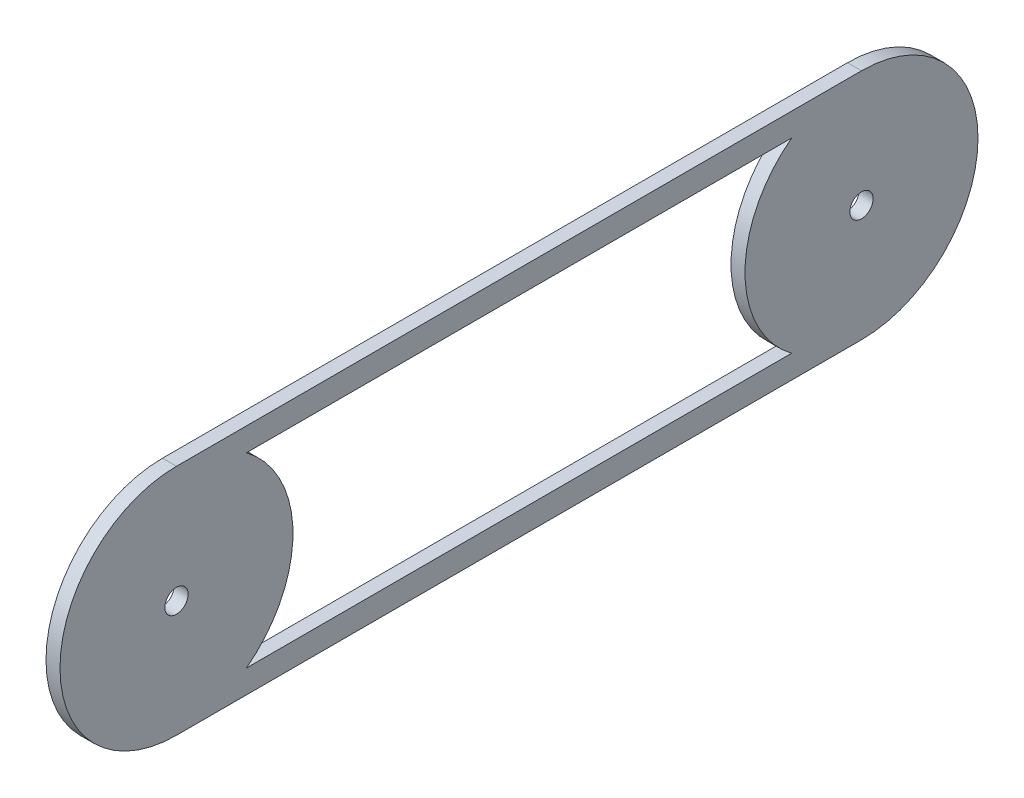
SolidWorks part; units mm, degrees
ref_plane "Front Plane" through (0, 0, 0) normal (0, 0, 1) x (1, 0, 0)
ref_plane "Top Plane" through (0, 0, 0) normal (0, 1, 0) x (1, 0, 0)
ref_plane "Right Plane" through (0, 0, 0) normal (1, 0, 0) x (0, 0, -1)
sketch "Sketch1" plane through (0, 0, 0) normal (1, 0, 0) x (0, 0, -1)
  line L0 (0, 25) -> (-147, 25)
  line L1 (0, -25) -> (-147, -25)
  line L2 (0, 20) -> (-147, 20)
  line L3 (0, -20) -> (-147, -20)
  arc A1 (0, 25) -> (0, -25) centre (0, 0) cw
  arc A2 (-147, 25) -> (-147, -25) centre (-147, 0) ccw
  arc A3 (-147, 20) -> (-147, -20) centre (-147, 0) ccw
  arc A4 (0, 20) -> (0, -20) centre (0, 0) cw
  circle A5 centre (-147, 0) radius 25
  circle A6 centre (0, 0) radius 25
  circle A7 centre (-147, 0) radius 2.5
  circle A8 centre (0, 0) radius 2.5
  dimension "D1" = 25
  dimension "D5" = 5
  dimension "D4" = 5
  dimension "D2" = 147
  dimension "D3" = 5
extrude "Boss-Extrude1" add sketch "Sketch1" along normal blind 3 contours L2 A5 A2 L3 A3 | L3 A5 L2 A3 | A6 L0 A5 L2 | A1 A6 L2 A4 L3 | L2 A6 L3 A4 | A6 L3 A5 L1 region at (0, 22.5778, 73.5) region at (0, 17.2249, -17.2249) region at (0, 23.1096, 139.2968) region at (0, 0, 3.0237) region at (0, -22.5778, 73.5) region at (0, 0, 143.9763)
